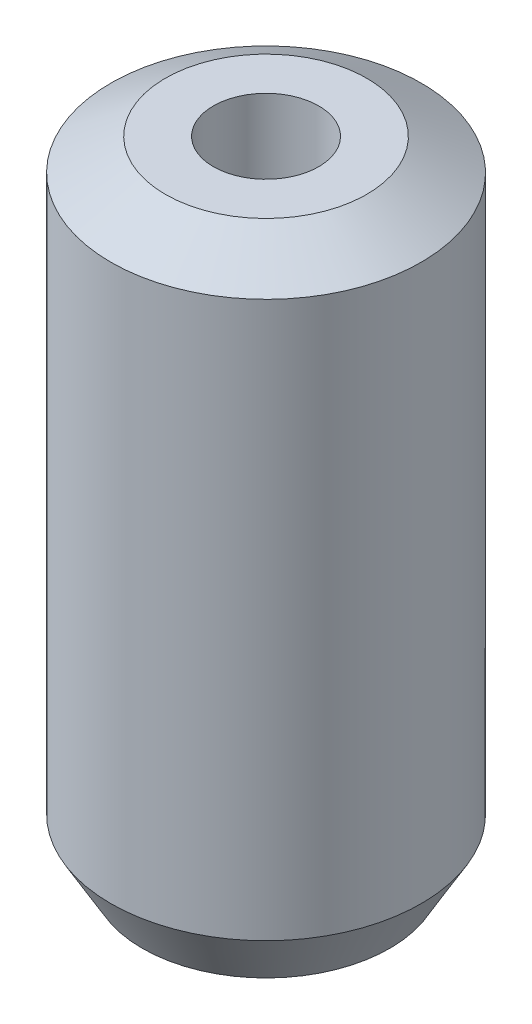
SolidWorks part; units mm, degrees
ref_plane "Front Plane" through (0, 0, 0) normal (0, 0, 1) x (1, 0, 0)
ref_plane "Top Plane" through (0, 0, 0) normal (0, 1, 0) x (1, 0, 0)
ref_plane "Right Plane" through (0, 0, 0) normal (1, 0, 0) x (0, 0, -1)
sketch "Sketch1" plane through (0, 0, 0) normal (0, 1, 0) x (1, 0, 0)
  circle A0 centre (0, 0) radius 27.5
  dimension "SHAFT_OD" = 55
extrude "Boss-Extrude1" add sketch "Sketch1" along normal blind 113.6673
sketch "Sketch2" plane through (0, 0, 0) normal (0, 1, 0) x (1, 0, 0)
  circle A0 centre (0, 0) radius 9.3359
  dimension "BORE_D" = 18.6718
extrude "Cut-Extrude1" cut sketch "Sketch2" along normal through all
chamfer "Chamfer1" distance 5.578 angle 60 2 edges at (0, 113.6673, 27.5) (0, 0, 27.5) first distance on face at (0, 113.6673, 27.5) first distance on face at (0, 0, 9.3359)
